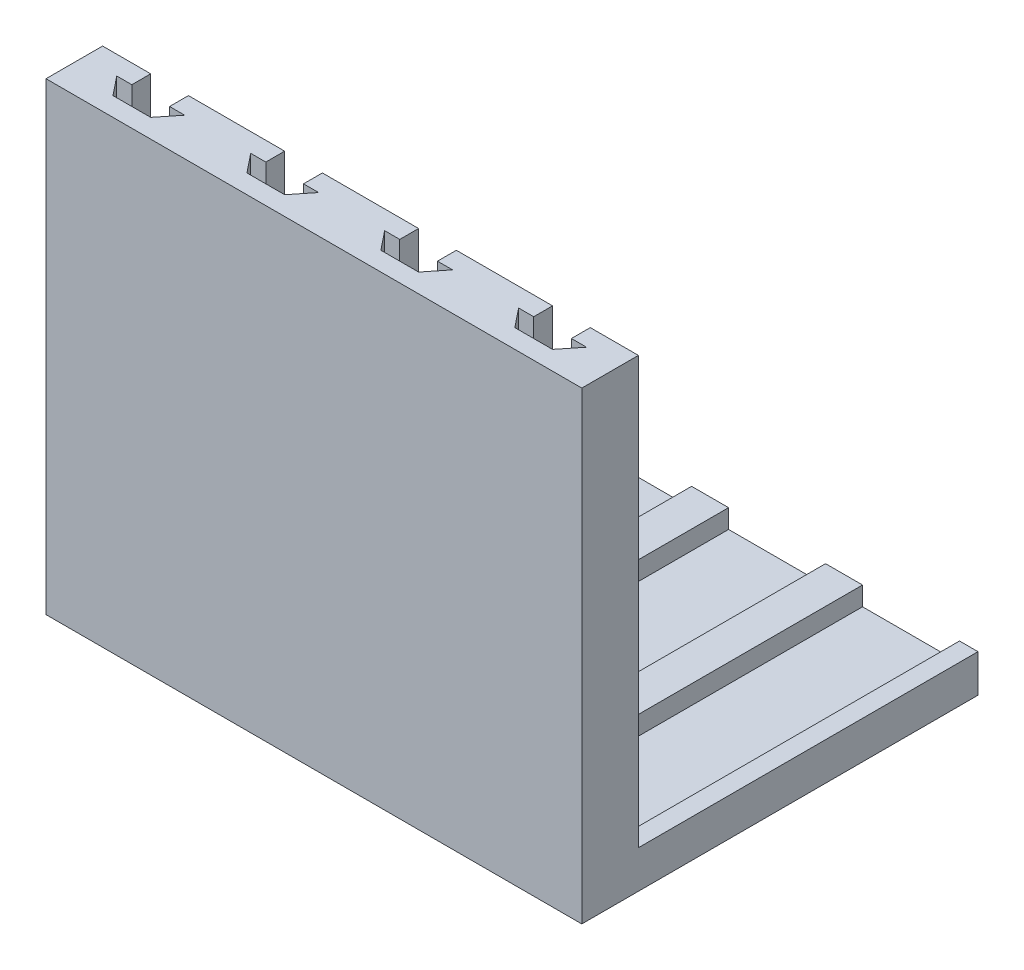
SolidWorks part; units mm, degrees
ref_plane "Front Plane" through (0, 0, 0) normal (0, 0, 1) x (1, 0, 0)
ref_plane "Top Plane" through (0, 0, 0) normal (0, 1, 0) x (1, 0, 0)
ref_plane "Right Plane" through (0, 0, 0) normal (1, 0, 0) x (0, 0, -1)
sketch "Sketch1" plane through (0, 0, 0) normal (0, 1, 0) x (1, 0, 0)
  line L1 (-17.75, -52.5) -> (17.75, -52.5)
  line L2 (-17.75, -52.5) -> (-17.75, 52.5)
  line L3 (-17.75, 52.5) -> (17.75, 52.5)
  line L4 (17.75, -52.5) -> (17.75, 52.5)
  line L5 (-17.75, -52.5) -> (17.75, 52.5) construction
  line L6 (-17.75, 52.5) -> (17.75, -52.5) construction
  point P0 (0, 0)
  dimension "D1" = 35.5
  dimension "D2" = 105
extrude "Boss-Extrude1" add sketch "Sketch1" along normal blind 10
sketch "Sketch2" plane through (0, 10, 0) normal (0, 1, 0) x (1, 0, 0)
  line L0 (17.75, -52.5) -> (17.75, 52.5) construction
  line L1 (-17.75, -52.5) -> (17.75, -52.5)
  line L2 (-17.75, -52.5) -> (-17.75, -37.5)
  line L3 (-17.75, -37.5) -> (17.75, -37.5)
  line L4 (17.75, -52.5) -> (17.75, -37.5)
  dimension "D1" = 15
extrude "Boss-Extrude2" add sketch "Sketch2" along normal blind 113
sketch "Sketch5" plane through (0, 10, 0) normal (0, 1, 0) x (1, 0, 0)
  line L0 (17.75, 52.5) -> (-17.75, 52.5) construction
  line L1 (12.85, 52.5) -> (-12.85, 52.5)
  line L2 (12.85, 52.5) -> (12.85, -37.5)
  line L3 (12.85, -37.5) -> (-12.85, -37.5)
  line L4 (-12.85, 52.5) -> (-12.85, -37.5)
  line L5 (17.75, -37.5) -> (-17.75, -37.5) construction
  line L6 (0, 52.5) -> (0, -37.5) construction
  line L7 (-17.75, 52.5) -> (-17.75, -37.5) construction
  dimension "D1" = 25.7
  dimension "D2" = 4.9
extrude "Cut-Extrude2" cut sketch "Sketch5" against normal blind 5
sketch "Sketch6" plane through (0, 123, 0) normal (0, 1, 0) x (1, 0, 0)
  line L0 (17.75, -37.5) -> (-17.75, -37.5) construction
  line L1 (-5, -37.5) -> (5, -37.5)
  line L2 (-5, -37.5) -> (-5, -42.5)
  line L4 (5, -37.5) -> (5, -42.5)
  line L5 (0, -37.5) -> (0, -52.5) construction
  line L6 (-17.75, -52.5) -> (17.75, -52.5) construction
  line L9 (-5, -42.5) -> (-9, -42.5)
  line L10 (-9, -42.5) -> (-5, -47.5)
  line L11 (-5, -47.5) -> (5, -47.5)
  line L12 (5, -42.5) -> (9, -42.5)
  line L13 (9, -42.5) -> (5, -47.5)
  dimension "D1" = 10
  dimension "D2" = 5
  dimension "D3" = 5
  dimension "D4" = 4
extrude "Cut-Extrude3" cut sketch "Sketch6" against normal blind 50
sketch "Sketch7" plane through (0, 73, 0) normal (0, 1, 0) x (1, 0, 0)
  line L0 (5, -42.5) -> (5, -37.5) construction
  line L1 (-5, -37.5) -> (5, -37.5)
  line L2 (-5, -37.5) -> (-5, -39.5)
  line L3 (-5, -39.5) -> (5, -39.5)
  line L4 (5, -37.5) -> (5, -39.5)
  dimension "D1" = 2
extrude "Cut-Extrude4" cut sketch "Sketch7" against normal blind 68
pattern_linear "LPattern1" count 4 spacing 35.5 along (-1, 0, 0) of "Boss-Extrude1", "Boss-Extrude2", "Cut-Extrude2", "Cut-Extrude3", "Cut-Extrude4"
